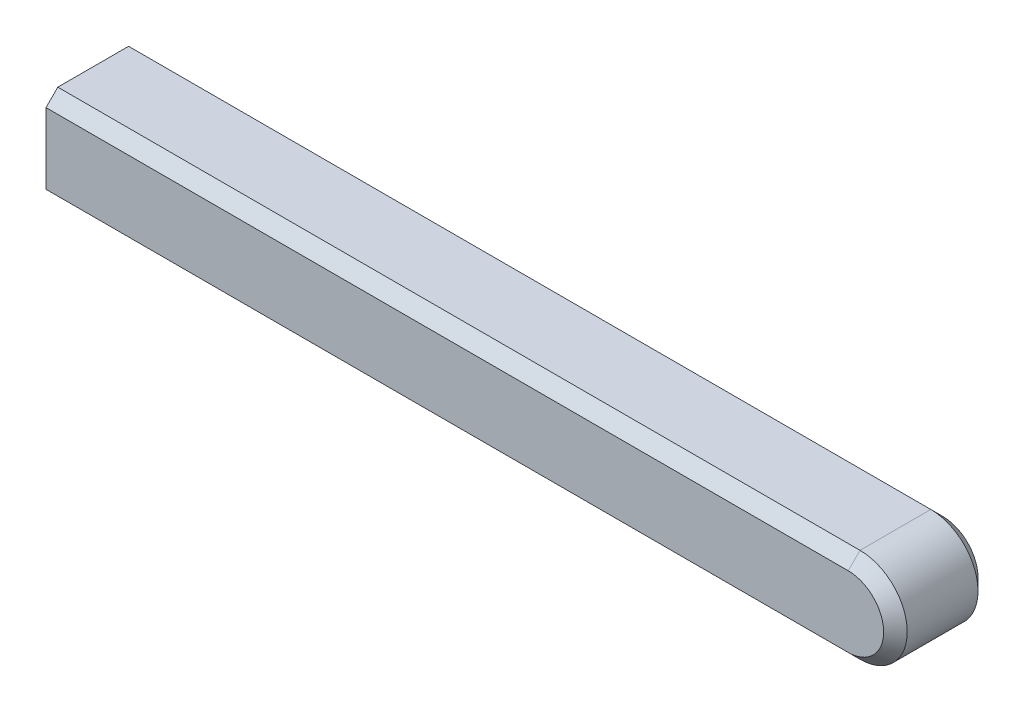
SolidWorks part; units mm, degrees
ref_plane "Front" through (0, 0, 0) normal (0, 0, 1) x (1, 0, 0)
ref_plane "Top" through (0, 0, 0) normal (0, 1, 0) x (1, 0, 0)
ref_plane "Right" through (0, 0, 0) normal (1, 0, 0) x (0, 0, -1)
sketch "body" plane through (0, 0, 0) normal (0, 0, 1) x (1, 0, 0)
  line L1 (0, 0) -> (17, 0)
  line L2 (0, 0) -> (0, 2)
  line L3 (0, 2) -> (17, 2)
  arc A0 (17, 0) -> (17, 2) centre (17, 1) ccw
  dimension "Width" = 2
  dimension "Length" = 18
extrude "Extrude1" add sketch "body" along normal blind 2
chamfer "Chamfer1" distance 0.25 6 edges at (8.5, 2, 0) (18, 1, 0) (8.5, 0, 0) (8.5, 2, 2) (18, 1, 2) (8.5, 0, 2)
